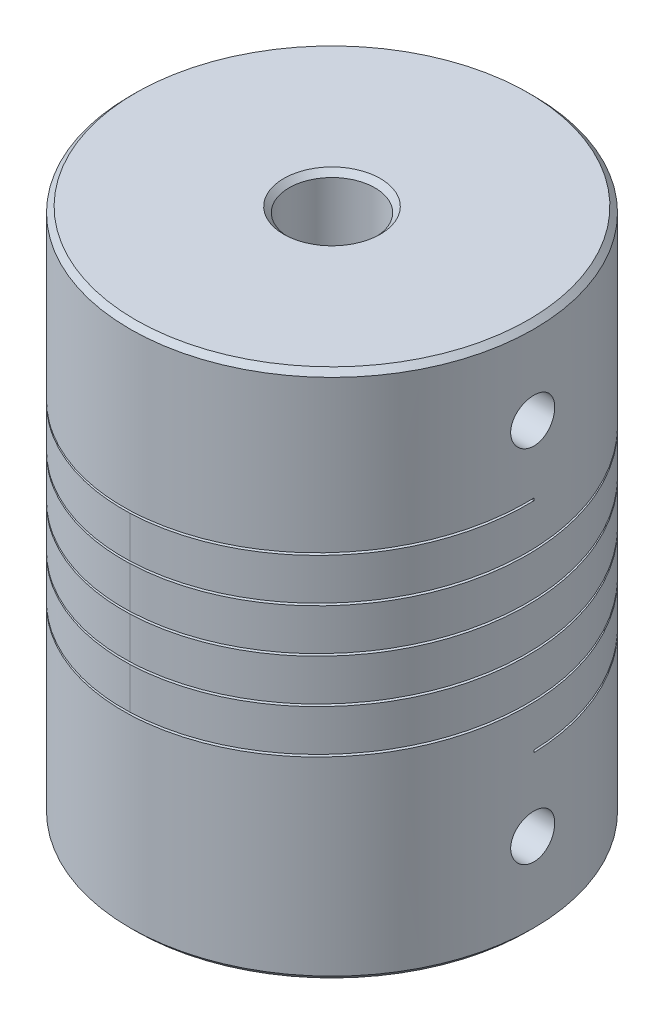
SolidWorks part; units mm, degrees
ref_plane "Front Plane" through (0, 0, 0) normal (0, 0, 1) x (1, 0, 0)
ref_plane "Top Plane" through (0, 0, 0) normal (0, 1, 0) x (1, 0, 0)
ref_plane "Right Plane" through (0, 0, 0) normal (1, 0, 0) x (0, 0, -1)
sketch "Sketch1" plane through (0, 0, 0) normal (0, 1, 0) x (1, 0, 0)
  circle A0 centre (0, 0) radius 9.398
  circle A1 centre (0, 0) radius 2
  dimension "D1" = 4
  dimension "D2" = 18.796
extrude "Boss-Extrude1" add sketch "Sketch1" along normal mid plane 24.638
sketch "Sketch6" plane through (0, 12.319, 0) normal (0, 1, 0) x (1, 0, 0)
  circle A0 centre (0, 0) radius 2
  dimension "D1" = 4
extrude "Cut-Extrude2" [suppressed] cut sketch "Sketch6" against normal blind 12.319
chamfer "Chamfer1" distance 0.25 angle 45 4 edges at (0, -12.319, 2) (0, -12.319, 9.398) (0, 12.319, 2) (0, 12.319, 9.398)
hole_wizard "M2.5x0.45 Tapped Hole1" positions "3DSketch1" profile "Sketch2" tap size "M2.5x0.45" standard "ANSI Metric" end condition up to next
sketch3d "3DSketch1"
  line L0 (0, -8.382, -9.398) -> (0, -8.382, 0) construction
  line L3 (0, 12.319, 0) -> (0, -12.319, 0) construction
  line L6 (9.398, -8.382, 0) -> (0, -8.382, 0) construction
  line L8 (9.398, 8.382, 0) -> (0, 8.382, 0) construction
  line L11 (0, 8.382, -9.398) -> (0, 8.382, 0) construction
  circle A2 centre (0, -12.319, 0) radius 2.25 construction
  point P0 (9.398, 8.382, 0)
  point P2 (9.398, -8.382, 0)
  point P4 (0, 8.382, -9.398)
  point P6 (0, -8.382, -9.398)
  point P28 (0, -10.069, 0)
  dimension "D1" = 3.937
  dimension "D2" = 3.937
sketch "Sketch2" plane through (9.398, 8.382, 0) normal (0, 1, 0) x (0, 0, -1)
  line L0 (0, 0) -> (0, 7.398)
  line L1 (0, 7.398) -> (1.025, 7.398)
  line L2 (1.025, 7.398) -> (1.025, 0)
  line L5 (1.025, 0) -> (0, 0)
  line L11 (0, -6.35) -> (0, 107.95) construction
  dimension "Thru Tap Drill Dia." = 2.05
  dimension "Thru Tap Drill Depth" = 7.398
cosmetic thread "Hole Thread1" parameters "D2"=2.5
cosmetic thread "Hole Thread2" parameters "D2"=2.5
cosmetic thread "Hole Thread3" parameters "D2"=2.5
cosmetic thread "Hole Thread4" parameters "D2"=2.5
ref_plane "Plane1" through (0, -4.953, 0) normal (0, -1, 0) x (-1, 0, 0)
sketch "Sketch3" plane through (0, -4.953, 0) normal (0, -1, 0) x (-1, 0, 0)
  circle A0 centre (0, 0) radius 9.398 construction
  circle A1 centre (0, 0) radius 9.398
curve "Helix/Spiral1" pitch 2.032 height 10.16 radius 9.398 centre (0, -4.953, 0) axis (0, 1, 0) start towards (1, 0, 0)
sketch "Sketch4" plane through (0, 0, 0) normal (0, 0, 1) x (1, 0, 0)
  line L0 (9.398, -5.0055) -> (2, -5.0055)
  line L1 (9.398, -7.357) -> (9.398, 7.357) construction
  line L2 (9.398, -4.953) -> (2, -4.953) construction
  line L3 (-10.0628, -4.953) -> (10.0628, -4.953) construction
  line L5 (9.398, -5.0055) -> (9.398, -4.9005)
  line L6 (9.398, -4.9005) -> (2, -4.9005)
  line L7 (2, -4.9005) -> (2, -5.0055)
  line L8 (2, -5.0055) -> (2, -12.069) construction
  line L11 (-2, -12.069) -> (2, -12.069) construction
  line L12 (-2, -12.069) -> (2, -12.069) construction
  dimension "D1" = 0.105
sweep "Cut-Sweep3" cut profiles "Sketch4" path "Helix/Spiral1" align with end faces yes
equation "\"D1@Cut-Extrude2\"=\"D1@boss-extrude1\"/2"
